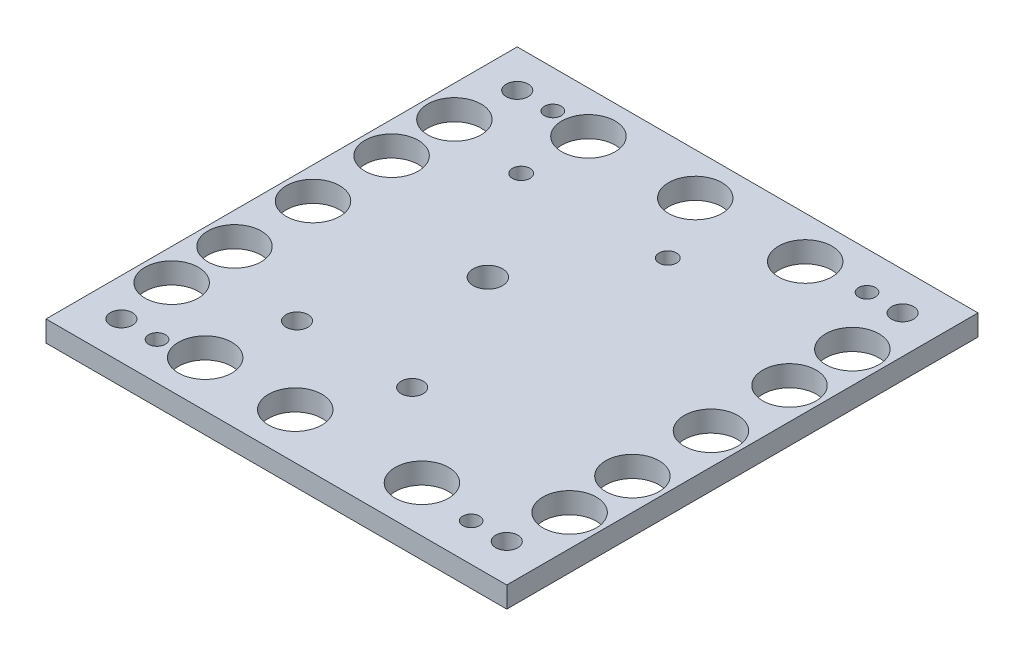
SolidWorks part; units mm, degrees
material "K110"
ref_plane "Front Plane" through (0, 0, 0) normal (0, 0, 1) x (1, 0, 0)
ref_plane "Top Plane" through (0, 0, 0) normal (0, 1, 0) x (1, 0, 0)
ref_plane "Right Plane" through (0, 0, 0) normal (1, 0, 0) x (0, 0, -1)
sketch "Sketch1" plane through (0, 0, 0) normal (0, 1, 0) x (1, 0, 0)
  line L1 (-110, -112.5) -> (110, -112.5)
  line L2 (-110, -112.5) -> (-110, 112.5)
  line L3 (-110, 112.5) -> (110, 112.5)
  line L4 (110, -112.5) -> (110, 112.5)
  line L5 (-110, -112.5) -> (110, 112.5) construction
  line L6 (-110, 112.5) -> (110, -112.5) construction
  point P0 (0, 0)
  dimension "D1" = 220
  dimension "D2" = 225
extrude "Boss-Extrude1" add sketch "Sketch1" along normal blind 10
sketch "Sketch2" plane through (0, 0, 0) normal (0, -1, 0) x (1, 0, 0)
  circle A0 centre (-56, 90.5) radius 12.75
  circle A1 centre (-13, 90.5) radius 12.75
  circle A2 centre (47.5, 90.5) radius 12.75
  circle A3 centre (95, 67.5) radius 12.75
  circle A4 centre (95, 37.5) radius 12.75
  circle A5 centre (95, 0) radius 12.75
  circle A6 centre (95, -37.5) radius 12.75
  circle A7 centre (95, -67.5) radius 12.75
  circle A8 centre (47.5, -92.5) radius 12.75
  circle A9 centre (-5, -92.5) radius 12.75
  circle A10 centre (-56, -92.5) radius 12.75
  circle A11 centre (-95, -67.5) radius 12.75
  circle A12 centre (-95, -37.5) radius 12.75
  circle A13 centre (-95, 0) radius 12.75
  circle A14 centre (-95, 37.5) radius 12.75
  circle A15 centre (-95, 67.5) radius 12.75
extrude "Cut-Extrude1" cut sketch "Sketch2" against normal up to next
sketch "Sketch3" plane through (0, 0, 0) normal (0, -1, 0) x (1, 0, 0)
  circle A0 centre (-21.75, -10.23) radius 7 construction
  circle A1 centre (-21.75, -10.23) radius 7
extrude "Cut-Extrude2" cut sketch "Sketch3" against normal up to next
hole_wizard "Ø8.0mm Dowel Hole1" positions "Sketch7" profile "Sketch5" hole size "Ø8.0" standard "ISO" end condition through all
sketch "Sketch7" plane through (0, 10, 0) normal (0, 1, 0) x (1, 0, 0)
  point P0 (75, -94.5)
  point P3 (-75, -94.5)
  point P6 (75, 94.5)
  point P10 (-75, 94.5)
sketch "Sketch5" plane through (75, 10, 94.5) normal (1, 0, 0) x (0, 0, 1)
  line L0 (0, 0) -> (0, 10)
  line L1 (0, 10) -> (4, 10)
  line L2 (4, 10) -> (4, 0)
  line L5 (4, 0) -> (0, 0)
  line L11 (0, -6.35) -> (0, 107.95) construction
  dimension "Thru Hole Dia." = 8
  dimension "Thru Hole Depth" = 10
hole_wizard "M10 Clearance Hole1" positions "Sketch10" profile "Sketch9" hole size "M10" standard "ISO" end condition through all
sketch "Sketch10" plane through (0, 10, 0) normal (0, 1, 0) x (1, 0, 0)
  point P0 (92, -94.5)
  point P3 (92, 94.5)
  point P6 (-92, 94.5)
  point P9 (-92, -94.5)
sketch "Sketch9" plane through (92, 10, 94.5) normal (1, 0, 0) x (0, 0, 1)
  line L0 (0, 0) -> (0, 10)
  line L1 (0, 10) -> (5.25, 10)
  line L2 (5.25, 10) -> (5.25, 0)
  line L5 (5.25, 0) -> (0, 0)
  line L11 (0, -6.35) -> (0, 107.95) construction
  dimension "Thru Hole Dia." = 10.5
  dimension "Thru Hole Depth" = 10
hole_wizard "M10 Clearance Hole2" positions "Sketch13" profile "Sketch12" hole size "M10" standard "ISO" end condition through all
sketch "Sketch13" plane through (0, 10, 0) normal (0, 1, 0) x (1, 0, 0)
  point P0 (5.75, -53.4)
  point P3 (-49.25, -53.4)
sketch "Sketch12" plane through (5.75, 10, 53.4) normal (1, 0, 0) x (0, 0, 1)
  line L0 (0, 0) -> (0, 10)
  line L1 (0, 10) -> (5.25, 10)
  line L2 (5.25, 10) -> (5.25, 0)
  line L5 (5.25, 0) -> (0, 0)
  line L11 (0, -6.35) -> (0, 107.95) construction
  dimension "Thru Hole Dia." = 10.5
  dimension "Thru Hole Depth" = 10
hole_wizard "M8 Clearance Hole1" positions "Sketch16" profile "Sketch15" hole size "M8" standard "ISO" end condition through all
sketch "Sketch16" plane through (0, 10, 0) normal (0, 1, 0) x (1, 0, 0)
  point P0 (13.25, 61.13)
  point P3 (-56.75, 61.13)
sketch "Sketch15" plane through (13.25, 10, -61.13) normal (1, 0, 0) x (0, 0, 1)
  line L0 (0, 0) -> (0, 10)
  line L1 (0, 10) -> (4.2, 10)
  line L2 (4.2, 10) -> (4.2, 0)
  line L5 (4.2, 0) -> (0, 0)
  line L11 (0, -6.35) -> (0, 107.95) construction
  dimension "Thru Hole Dia." = 8.4
  dimension "Thru Hole Depth" = 10
